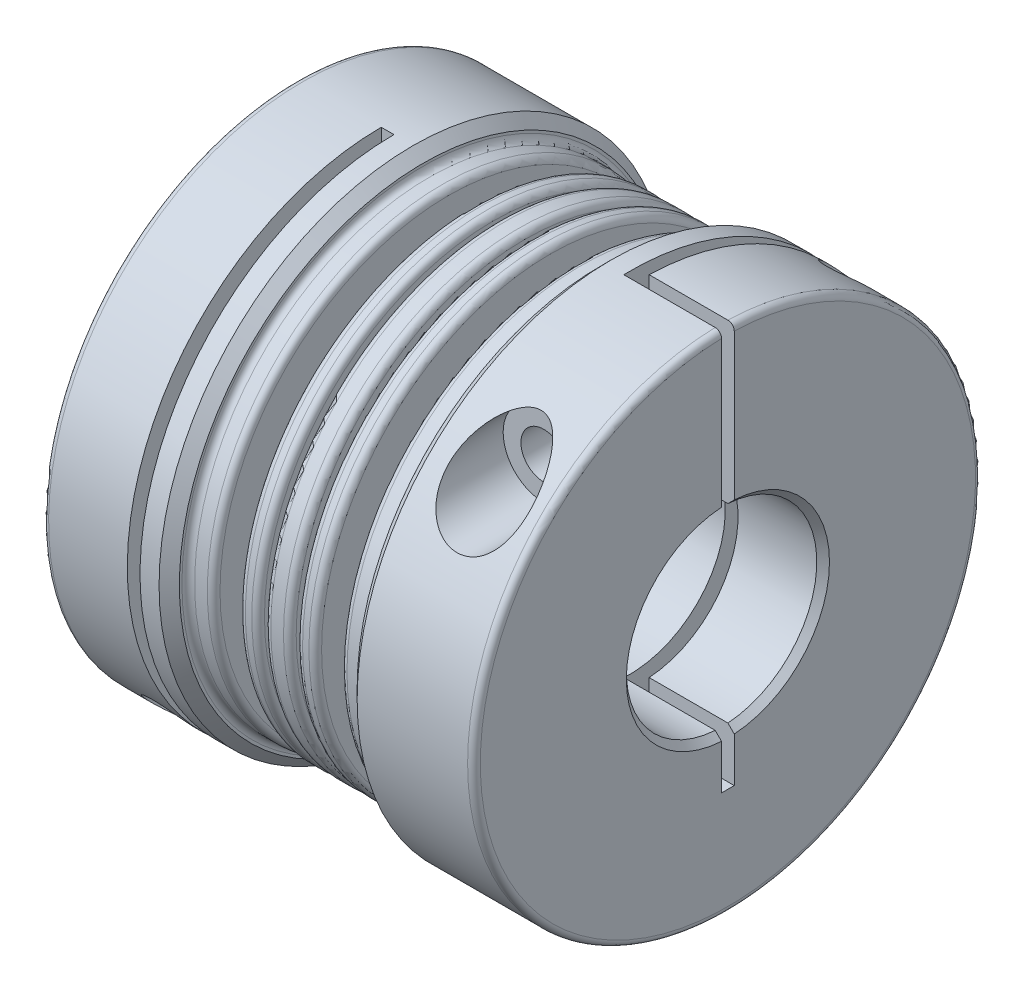
SolidWorks part; units mm, degrees
ref_plane "Front Plane" through (0, 0, 0) normal (0, 0, 1) x (1, 0, 0)
ref_plane "Top Plane" through (0, 0, 0) normal (0, 1, 0) x (1, 0, 0)
ref_plane "Right Plane" through (0, 0, 0) normal (1, 0, 0) x (0, 0, -1)
sketch "Sketch1" plane through (0, 0, 0) normal (0, 0, 1) x (1, 0, 0)
  line L0 (-17, 20) -> (-7, 20)
  line L3 (0, 12) -> (0, 7.5)
  line L4 (0, 7.5) -> (-17, 7.5)
  line L5 (-17, 7.5) -> (-17, 20)
  line L6 (-7, 20) -> (-7, 18.5)
  line L7 (-7, 18.5) -> (-5, 18.5)
  line L8 (-5, 18.5) -> (-5, 12)
  line L9 (-5, 12) -> (0, 12)
  line L10 (0, 0) -> (-19.8738, 0) construction
  dimension "D1" = 7.5
  dimension "D2" = 12
  dimension "D3" = 20
  dimension "D4" = 1.5
  dimension "D5" = 2
  dimension "D6" = 12
  dimension "D7" = 17
revolve "Revolve1" add sketch "Sketch1" angle 360 about L10
ref_plane "Plane1" through (-3, 0, 0) normal (1, 0, 0) x (0, 0, -1)
sketch "Sketch2" plane through (-3, 0, 0) normal (1, 0, 0) x (0, 0, -1)
  circle A0 centre (0, 0) radius 18.5
  circle A3 centre (0, 0) radius 18.5 construction
  circle A4 centre (0, 0) radius 7.5 construction
  circle A5 centre (0, 0) radius 7.5
extrude "Boss-Extrude1" add sketch "Sketch2" along normal blind 1.5
chamfer "Chamfer2" distance 0.8 angle 45 1 edges at (-7, 0, -20)
fillet "Fillet1" radius 0.5 2 edges at (-3, 0, -18.5) (-1.5, 0, -18.5)
ref_axis "Axis1" through (-17, 0, 0) along (1, 0, 0)
pattern_linear "LPattern1" count 2 spacing 2 along (1, 0, 0) of "Fillet1", "Boss-Extrude1"
fillet "Fillet2" radius 0.5 2 edges at (-5, 0, -18.5) (-7, 0, -18.5)
sketch "Sketch3" plane through (0, 0, 0) normal (0, 1, 0) x (1, 0, 0)
  line L0 (-17, 0) -> (-7.8, 0) construction
  line L1 (-9.3, 0.5) -> (-21.1556, 0.5)
  line L2 (-9.3, 0.5) -> (-9.3, -0.5)
  line L3 (-9.3, -0.5) -> (-21.1556, -0.5)
  line L4 (-21.1556, 0.5) -> (-21.1556, -0.5)
  line L5 (-9.3, 0.5) -> (-21.1556, -0.5) construction
  line L6 (-9.3, -0.5) -> (-21.1556, 0.5) construction
  line L7 (-7.8, 20) -> (-7.8, -20) construction
  point P0 (-15.2278, 0)
  dimension "D1" = 1.5
  dimension "D2" = 1
extrude "Cut-Extrude1" cut sketch "Sketch3" against normal up to next and the other way blind 11.5
sketch "Sketch5" plane through (0, 0, 0) normal (0, 0, 1) x (1, 0, 0)
  line L0 (-17, 0) -> (-7.8, 0) construction
  line L1 (-9.3, 0) -> (-10.3, 0)
  line L2 (-9.3, 0) -> (-9.3, -20)
  line L3 (-9.3, -20) -> (-10.3, -20)
  line L4 (-10.3, 0) -> (-10.3, -20)
  line L5 (-9.3, 0) -> (-10.3, -20) construction
  line L6 (-9.3, -20) -> (-10.3, 0) construction
  point P0 (-9.8, -10)
  dimension "D1" = 1
revolve "Cut-Revolve1" cut sketch "Sketch5" angle 180 about L1
ref_plane "Plane3" through (0, -14, 0) normal (0, 1, 0) x (1, 0, 0)
sketch "Sketch11" plane through (0, -14, 0) normal (0, 1, 0) x (1, 0, 0)
  line L0 (-15.7, 20) -> (-15.7, 10)
  line L1 (-7.8, 20) -> (-17, 20) construction
  line L2 (-15.7, 10) -> (-14.3, 10)
  line L3 (-14.3, 10) -> (-14.3, -22.0055)
  line L4 (-14.3, -22.0055) -> (-12.5, -22.0055)
  line L5 (-12.5, -22.0055) -> (-12.5, 20)
  line L6 (-12.5, 20) -> (-15.7, 20)
  line L7 (-17, 20) -> (-17, -20) construction
  dimension "D1" = 4.5
  dimension "D2" = 10
  dimension "D3" = 1.8
  dimension "D4" = 3.2
revolve "Cut-Revolve3" cut sketch "Sketch11" angle 360 about L5
fillet "Fillet3" radius 0.5 1 edges at (-17, 20, 0)
chamfer "Chamfer3" distance 0.5 angle 45 2 edges at (-17, 0, 7.5) (-17, 0, -7.5)
mirror "Mirror1" about plane through (0, 0, 0) normal (1, 0, 0) of bodies 107
move or copy body "Body-Move/Copy1" bodies to move or copy 108 copy no rotation origin (0, 0, 0) rotation axis (1, 0, 0) rotation angle 180
combine bodies "Combine1" operation type add bodies to combine 107 109
